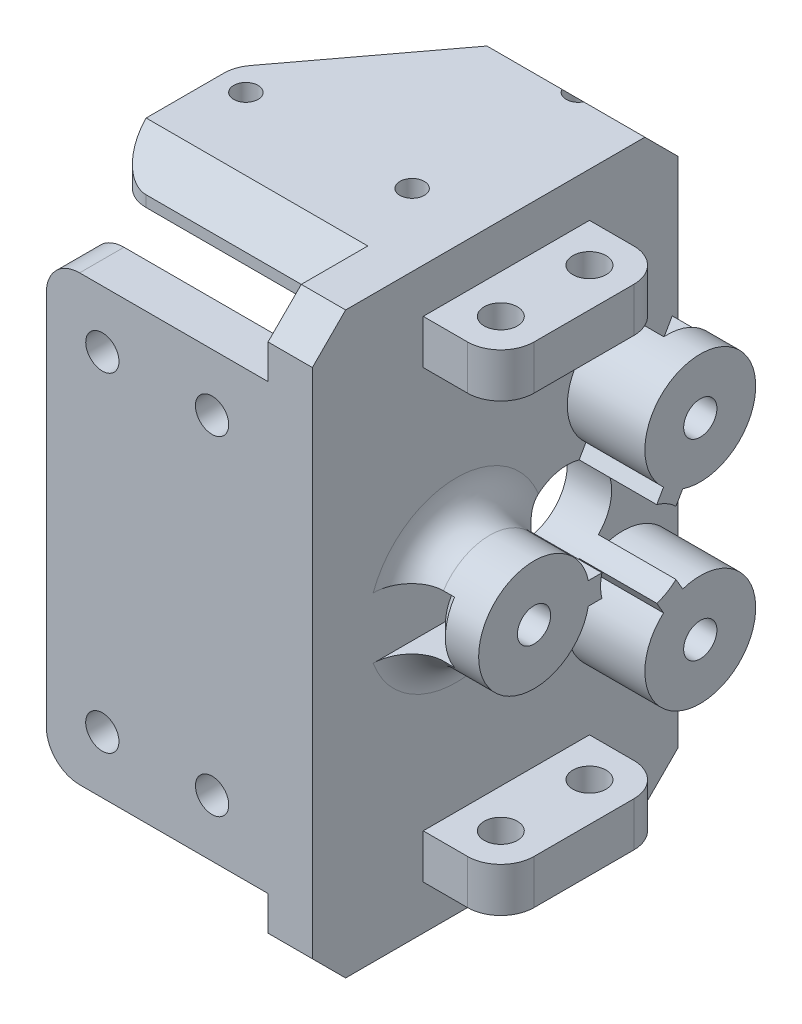
SolidWorks part; units mm, degrees
ref_plane "Спереди" through (0, 0, 0) normal (0, 0, 1) x (1, 0, 0)
ref_plane "Сверху" through (0, 0, 0) normal (0, 1, 0) x (1, 0, 0)
ref_plane "Справа" through (0, 0, 0) normal (1, 0, 0) x (0, 0, -1)
sketch "Sketch1" plane through (0, 0, 0) normal (0, 1, 0) x (1, 0, 0)
  line L5 (-12, -10) -> (12, -10)
  line L6 (-12, -10) -> (-12, 10)
  line L7 (-12, 10) -> (12, 10)
  line L8 (12, -10) -> (12, 10)
  line L9 (-12, -10) -> (12, 10) construction
  line L10 (-12, 10) -> (12, -10) construction
  point P0 (0, 0)
  dimension "D1" = 20
  dimension "D2" = 24
extrude "Boss-Extrude1" add sketch "Sketch1" along normal blind 52.2 contours L5 | L5 region at (0, 0, 0)
sketch "Sketch3" plane through (0, 0, 10) normal (0, 0, 1) x (1, 0, 0)
  line L0 (-12, 52.2) -> (-12, 0) construction
  line L1 (-12, 4) -> (8, 4)
  line L2 (-12, 4) -> (-12, 48.2)
  line L3 (-12, 48.2) -> (8, 48.2)
  line L4 (8, 4) -> (8, 48.2)
  line L5 (-12, 0) -> (12, 0) construction
  line L6 (12, 52.2) -> (12, 0) construction
  line L7 (-12, 52.2) -> (12, 52.2) construction
  dimension "D1" = 4
  dimension "D2" = 4
  dimension "D3" = 4
extrude "Cut-Extrude2" cut sketch "Sketch3" against normal blind 52.2
sketch "Sketch4" plane through (0, 52.2, 0) normal (0, 1, 0) x (1, 0, 0)
  line L0 (-12, 0) -> (-2, 0) construction
  line L1 (-12, -10) -> (-12, 10) construction
  line L2 (-2, 0) -> (-2, 5.3635) construction
  circle A0 centre (-9.5, -7.5) radius 1.1
  circle A1 centre (-9.5, 7.5) radius 1.1
  circle A2 centre (5.5, 7.5) radius 1.1
  circle A3 centre (5.5, -7.5) radius 1.1
  dimension "D1" = 2.2
  dimension "D3" = 15
  dimension "D4" = 15
  dimension "D2" = 10
extrude "Cut-Extrude3" cut sketch "Sketch4" against normal through all
sketch "Sketch5" plane through (0, 0, 0) normal (0, -1, 0) x (1, 0, 0)
  line L0 (-12, -10) -> (0, -10)
  line L1 (-12, -10) -> (12, -10) construction
  line L2 (-12, -10) -> (-12, 6)
  line L3 (-12, 10) -> (-12, -10) construction
  line L4 (-12, 6) -> (0, -10)
  dimension "D1" = 12
  dimension "D2" = 16
extrude "Cut-Extrude4" cut sketch "Sketch5" against normal through all
sketch "Sketch6" plane through (0, 0, 0) normal (0, -1, 0) x (1, 0, 0)
  line L5 (-12, 10) -> (-12, 6)
  line L6 (-12, 6) -> (0, -10)
  line L7 (0, -10) -> (12, -10)
  line L8 (12, -10) -> (12, 10)
  line L9 (12, 10) -> (-12, 10)
  line L10 (-12, 10) -> (-12, 6)
  line L11 (-12, 6) -> (0, -10)
  line L12 (0, -10) -> (12, -10)
  line L13 (12, -10) -> (12, 10)
  line L14 (12, 10) -> (-12, 10)
  dimension "D1" = 0
extrude "Boss-Extrude2" add sketch "Sketch6" against normal blind 4
sketch "Sketch7" plane through (0, 0, 0) normal (0, -1, 0) x (1, 0, 0)
  line L0 (-12, 6) -> (-12, -22.8253) construction
  line L2 (-2, 0) -> (-12, 0) construction
  circle A0 centre (-2, 0) radius 7 construction
  circle A1 centre (5, 0) radius 1.1
  circle A2 centre (-2, -7) radius 1.1
  circle A3 centre (-9, 0) radius 1.1
  circle A4 centre (-2, 7) radius 1.1
  point P17 (-2, 0)
  dimension "D2" = 14
  dimension "D3" = 2.2
  dimension "D1" = 10
  dimension "D4" = 4
extrude "Cut-Extrude5" cut sketch "Sketch7" against normal blind 4
sketch "Sketch8" plane through (0, 0, 10) normal (0, 0, 1) x (1, 0, 0)
  line L8 (8, 4) -> (-12, 4)
  line L9 (-12, 4) -> (-12, 0)
  line L10 (-12, 0) -> (12, 0)
  line L11 (12, 0) -> (12, 52.2)
  line L12 (12, 52.2) -> (-12, 52.2)
  line L13 (-12, 52.2) -> (-12, 48.2)
  line L14 (-12, 48.2) -> (8, 48.2)
  line L15 (8, 48.2) -> (8, 4)
  line L16 (8, 4) -> (-12, 4)
  line L18 (-12, 0) -> (12, 0)
  line L19 (12, 0) -> (12, 52.2)
  line L20 (12, 52.2) -> (-12, 52.2)
  line L21 (-12, 52.2) -> (-12, 48.2)
  line L22 (-12, 48.2) -> (8, 48.2)
  line L23 (8, 48.2) -> (8, 4)
  line L24 (-12, 4) -> (-12, 0)
  dimension "D1" = 0
extrude "Boss-Extrude3" add sketch "Sketch8" along normal blind 7
sketch "Sketch9" plane through (0, 0, 17) normal (0, 0, 1) x (1, 0, 0)
  line L0 (-12, 0) -> (12, 0) construction
  line L1 (12, 52.2) -> (8, 52.2)
  line L2 (12, 52.2) -> (12, 0)
  line L3 (12, 0) -> (8, 0)
  line L4 (8, 52.2) -> (8, 0)
  dimension "D1" = 4
extrude "Boss-Extrude4" add sketch "Sketch9" along normal blind 6
sketch "Sketch12" plane through (8, 0, 0) normal (-1, 0, 0) x (0, 0, 1)
  line L0 (23, 52.2) -> (23, 0) construction
  line L1 (27, 46.1) -> (19, 46.1)
  line L2 (27, 46.1) -> (27, 6.1)
  line L3 (27, 6.1) -> (19, 6.1)
  line L4 (19, 46.1) -> (19, 6.1)
  line L5 (27, 46.1) -> (19, 6.1) construction
  line L6 (27, 6.1) -> (19, 46.1) construction
  point P0 (23, 26.1)
  line M5 (23, 0) -> (23, 52.2)
  dimension "D1" = 40
  dimension "D2" = 8
extrude "Boss-Extrude5" add sketch "Sketch12" along normal blind 20 contours L1 L4 L3 M5 region at (8, 26.1, 21)
sketch "Sketch13" plane through (0, 0, 23) normal (0, 0, 1) x (1, 0, 0)
  line L0 (8, 46.1) -> (-12, 6.1) construction
  line L1 (2.7339, 26.1) -> (-2.0002, 26.0996) construction
  line L2 (-2.0002, 26.0996) -> (-2.0002, 35.2652) construction
  circle A0 centre (2.9498, 40.95) radius 1.5
  circle A1 centre (2.9523, 11.25) radius 1.5
  circle A2 centre (-6.9527, 11.25) radius 1.5
  circle A3 centre (-6.9502, 40.95) radius 1.5
  dimension "D1" = 3
  dimension "D2" = 9.9
  dimension "D3" = 29.7
extrude "Cut-Extrude6" cut sketch "Sketch13" against normal blind 20
chamfer "Chamfer3" distance 3 angle 45 6 edges at (-2, 0, 17) (-2, 52.2, 17) (10, 52.2, 23) (6, 52.2, -10) (10, 0, 23) (6, 0, -10)
fillet "Fillet2" radius 3 8 edges at (0, 3.5, -10) (-12, 2, 6) (-12, 50.2, 6) (0, 48.7, -10) (-12, 48.7, 17) (-12, 46.1, 21) (-12, 3.5, 17) (-12, 6.1, 21)
sketch "Sketch14" plane through (12, 0, 0) normal (1, 0, 0) x (0, 0, -1)
  line L0 (0, 52.2) -> (0, 0) construction
  line L1 (-20, 52.2) -> (7, 52.2) construction
  line L2 (-20, 0) -> (7, 0) construction
  line L3 (10, 49.2) -> (10, 3) construction
  circle A1 centre (0, 26.1) radius 4
  circle A2 centre (0, 26.1) radius 8
  dimension "D1" = 10
  dimension "D2" = 8
  dimension "D3" = 4
extrude "Cut-Extrude7" cut sketch "Sketch14" against normal blind 10 contours L0 A1 | A1 L0 region at (12, 26.1, -1.6977) region at (12, 26.1, 1.6977)
sketch "Sketch16" plane through (12, 0, 0) normal (1, 0, 0) x (0, 0, -1)
  line L0 (0, 26.1) -> (-25.7538, 26.1) construction
  circle A0 centre (-10, 26.1) radius 5
  point P12 (0, 26.1)
  dimension "D1" = 10
  dimension "D2" = 10
extrude "Boss-Extrude6" add sketch "Sketch16" along normal blind 7
sketch "Sketch17" plane through (12, 0, 0) normal (1, 0, 0) x (0, 0, -1)
  line L0 (-11.5877, 28.85) -> (-21.3317, 28.85)
  line L1 (-6.8246, 26.1) -> (-8.4123, 28.85)
  line L2 (-8.4123, 28.85) -> (-11.5877, 28.85)
  line L3 (-11.5877, 28.85) -> (-13.1754, 26.1)
  line L4 (-13.1754, 26.1) -> (-11.5877, 23.35)
  line L5 (-11.5877, 23.35) -> (-8.4123, 23.35)
  line L6 (-8.4123, 23.35) -> (-6.8246, 26.1)
  line L7 (-21.3317, 28.85) -> (-21.3317, 23.35)
  line L8 (-21.3317, 23.35) -> (-11.5877, 23.35)
  circle A0 centre (-10, 26.1) radius 2.75 construction
  circle M1 centre (-10, 26.1) radius 5
  dimension "D1" = 5.5
extrude "Cut-Extrude8" cut sketch "Sketch17" along normal blind 3 contours L7 L8 L0 M1 | L5 L6 L1 L2 L3 L4 | L8 L4 L3 L0 M1 region at (12, 26.1, 13.5261) region at (12, 26.1, 10) region at (12, 26.1, 18.0289)
sketch "Sketch18" plane through (19, 0, 0) normal (1, 0, 0) x (0, 0, -1)
  circle A0 centre (-10, 26.1) radius 1.5
  dimension "D1" = 3
extrude "Cut-Extrude9" cut sketch "Sketch18" against normal blind 7
chamfer "Chamfer4" distance 1 angle 45 1 edges at (15, 26.1, 15)
sketch "Sketch19" plane through (12, 0, 0) normal (1, 0, 0) x (0, 0, -1)
  line L1 (-2, 27.1) -> (-6, 27.1)
  line L2 (-2, 27.1) -> (-2, 25.1)
  line L3 (-2, 25.1) -> (-6, 25.1)
  line L4 (-6, 27.1) -> (-6, 25.1)
  line L5 (-2, 27.1) -> (-6, 25.1) construction
  line L6 (-2, 25.1) -> (-6, 27.1) construction
  circle A0 centre (0, 26.1) radius 4 construction
  point P0 (-4, 26.1)
  arc M23 (-14.1758, 28.85) -> (-14.1758, 23.35) centre (-10, 26.1) cw
  circle M28 centre (0, 26.1) radius 4
  dimension "D1" = 2
  dimension "D2" = 4
extrude "Boss-Extrude7" add sketch "Sketch19" along normal blind 7 contours L3 L1 M28 M23 region at (12, 26.1, 4.4955)
pattern_circular "CirPattern1" count 3 over 360 about axis through (2, 26.1, 0) along (1, 0, 0) of "Boss-Extrude6", "Cut-Extrude8", "Cut-Extrude9", "Chamfer4", "Boss-Extrude7" reverse direction yes
sketch "Sketch21" plane through (12, 0, 0) normal (1, 0, 0) x (0, 0, -1)
  line L0 (-20, 0) -> (7, 0) construction
  line L1 (-13, 4) -> (2, 4)
  line L2 (-13, 4) -> (-13, 8)
  line L3 (-13, 8) -> (2, 8)
  line L4 (2, 4) -> (2, 8)
  line L5 (-13, 4) -> (2, 8) construction
  line L6 (-13, 8) -> (2, 4) construction
  line L7 (10, 17.4397) -> (10, 3) construction
  line L8 (0, 26.1) -> (-26.3475, 26.1) construction
  point P0 (-5.5, 6)
  dimension "D1" = 4
  dimension "D2" = 15
  dimension "D3" = 4
  dimension "D4" = 8
extrude "Boss-Extrude8" add sketch "Sketch21" along normal up to surface (7 mm away)
fillet "Fillet3" radius 3 2 edges at (19, 6, 13) (19, 6, -2)
sketch "Sketch22" plane through (0, 4, 0) normal (0, -1, 0) x (1, 0, 0)
  line L0 (19, 5.5) -> (13.2888, 5.5) construction
  line L1 (19, 10) -> (19, 1) construction
  line L2 (12, 20) -> (12, -7) construction
  circle A0 centre (15.5, 9.5) radius 1.5
  circle A2 centre (15.5, 1.5) radius 1.5
  dimension "D1" = 3
  dimension "D2" = 8
  dimension "D3" = 3.5
extrude "Cut-Extrude10" cut sketch "Sketch22" against normal blind 10
sketch "Sketch23" plane through (12, 0, 0) normal (1, 0, 0) x (0, 0, -1)
  line L0 (0, 26.1) -> (13.0368, 26.1) construction
ref_plane "Plane1" through (0, 26.1, 0) normal (0, 1, 0) x (1, 0, 0)
mirror "Mirror1" about plane through (0, 26.1, 0) normal (0, 1, 0) of "Boss-Extrude8", "Fillet3", "Cut-Extrude10"
fillet "Fillet4" radius 3 2 edges at (12, 21.1905, 9.0532) (12, 31.0095, 9.0532)
